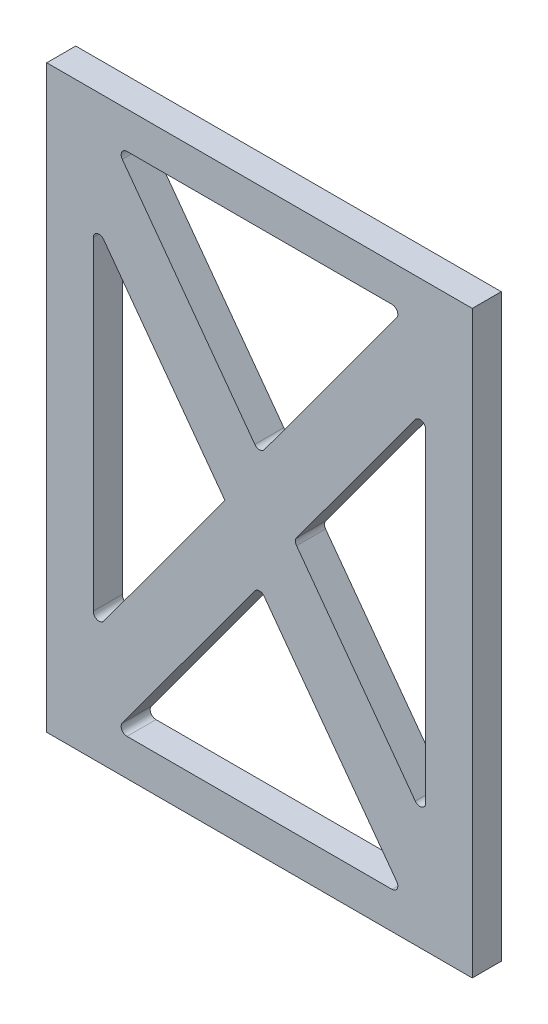
SolidWorks part; units mm, degrees
ref_plane "Front Plane" through (0, 0, 0) normal (0, 0, 1) x (1, 0, 0)
ref_plane "Top Plane" through (0, 0, 0) normal (0, 1, 0) x (1, 0, 0)
ref_plane "Right Plane" through (0, 0, 0) normal (1, 0, 0) x (0, 0, -1)
sketch "Sketch1" plane through (0, 0, 0) normal (0, 0, 1) x (1, 0, 0)
  line L0 (0, 100) -> (73.3793, 0) construction
  line L1 (0, 0) -> (73.3793, 0)
  line L2 (0, 0) -> (0, 100)
  line L3 (73.3793, 100) -> (0, 100)
  line L4 (73.3793, 0) -> (73.3793, 100)
  line L5 (0, 0) -> (73.3793, 100) construction
  line L6 (8.0215, 80.9465) -> (30.7298, 50)
  line L7 (11.8612, 93.6803) -> (61.5181, 93.6803)
  line L8 (8.0215, 80.9465) -> (8.0215, 19.0535)
  line L9 (11.8612, 6.3197) -> (61.5181, 6.3197)
  line L10 (65.3578, 80.9465) -> (65.3578, 19.0535)
  line L11 (30.7298, 50) -> (8.0215, 19.0535)
  line L12 (36.6897, 53.2702) -> (36.6897, 83.0042) construction
  line L13 (42.6495, 50) -> (65.3578, 19.0535)
  line L14 (65.3578, 80.9465) -> (42.6495, 50)
  line L15 (11.8612, 93.6803) -> (36.6897, 59.8445)
  line L16 (36.6897, 59.8445) -> (61.5181, 93.6803)
  line L17 (2.9368, 50) -> (79.1746, 50) construction
  line L18 (11.8612, 6.3197) -> (36.6897, 40.1555)
  line L19 (36.6897, 40.1555) -> (61.5181, 6.3197)
  point P0 (75.8928, 108.9365)
  point P5 (36.6897, 50)
  point P8 (0, 0)
  point P29 (36.6897, 100)
  point P31 (0, 50)
  dimension "D1" = 100
extrude "Boss-Extrude1" add sketch "Sketch1" along normal blind 5
fillet "Fillet1" radius 1 11 edges at (8.0215, 19.0535, 2.5) (36.6897, 40.1555, 2.5) (61.5181, 6.3197, 2.5) (11.8612, 6.3197, 2.5) (65.3578, 19.0535, 2.5) (42.6495, 50, 2.5) (65.3578, 80.9465, 2.5) (36.6897, 59.8445, 2.5) (61.5181, 93.6803, 2.5) (11.8612, 93.6803, 2.5) (8.0215, 80.9465, 2.5)
